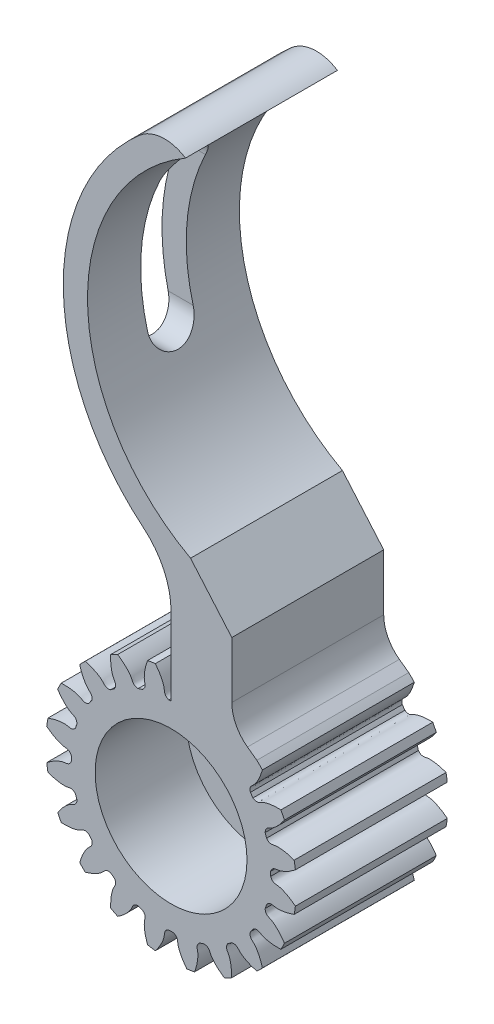
SolidWorks part; units mm, degrees
material "聚脂树脂"
ref_plane "前视基准面" through (0, 0, 0) normal (0, 0, 1) x (1, 0, 0)
ref_plane "上视基准面" through (0, 0, 0) normal (0, 1, 0) x (1, 0, 0)
ref_plane "右视基准面" through (0, 0, 0) normal (1, 0, 0) x (0, 0, -1)
other "Configuration Table"
sketch "草图1" plane through (0, 0, 0) normal (0, 0, 1) x (1, 0, 0)
  circle A0 centre (0, 0) radius 16.5
extrude "凸台-拉伸1" add sketch "草图1" along normal blind 20
ref_axis "基准轴1" through (0, 0, -1.5) along (0, 0, 1)
sketch "草图2" plane through (0, 0, 0) normal (0, 0, 1) x (1, 0, 0)
  line L0 (0, 0) -> (0, 16.5) construction
  circle A0 centre (0, 0) radius 16.5 construction
  arc A1 (0.29, 13.1218) -> (-0.29, 13.1218) centre (0, 0) ccw
  arc A2 (4.7717, 18.7474) -> (-4.7717, 18.7474) centre (0, 0) ccw
  spline S0 degree 3 poles (0.29, 13.1218) (0.9168, 13.3402) (0.8356, 13.7807) (0.9193, 14.205) (0.9283, 14.2463) (0.9395, 14.293) (0.9529, 14.3448) (0.969, 14.4018) (0.9878, 14.4638) (1.0095, 14.5309) (1.0345, 14.6028) (1.0629, 14.6795) (1.0948, 14.7608) (1.1305, 14.8467) (1.1702, 14.9371) (1.2141, 15.0317) (1.2623, 15.1305) (1.315, 15.2334) (1.3725, 15.3401) (1.4349, 15.4506) (1.5023, 15.5646) (1.575, 15.6821) (1.653, 15.8029) (1.7366, 15.9267) (1.826, 16.0534) (1.9211, 16.1829) (2.0223, 16.3149) (2.1296, 16.4493) (2.2432, 16.5859) (2.3632, 16.7244) (2.4897, 16.8646) (2.6229, 17.0065) (2.7628, 17.1496) (2.9095, 17.2939) (3.0632, 17.4391) (3.224, 17.585) (3.3918, 17.7313) (3.567, 17.8779) (3.7493, 18.0245) (3.9391, 18.1709) (4.1363, 18.3167) (4.4122, 18.5125) (4.6259, 18.6545) (4.7717, 18.7474) knots 0 0 0 0 0.165916 0.170906 0.176664 0.183189 0.190482 0.198542 0.207371 0.216967 0.22733 0.238462 0.250361 0.263027 0.276462 0.290664 0.305634 0.321371 0.337876 0.355149 0.37319 0.391998 0.411574 0.431917 0.453028 0.474907 0.497554 0.520968 0.54515 0.570099 0.595817 0.622302 0.649554 0.677575 0.706363 0.735918 0.766242 0.797333 0.829191 0.861818 0.895212 0.929373 1 1 1 1
  spline S1 degree 3 poles (-0.29, 13.1218) (-0.9168, 13.3402) (-0.8356, 13.7807) (-0.9193, 14.205) (-0.9283, 14.2463) (-0.9395, 14.293) (-0.9529, 14.3448) (-0.969, 14.4018) (-0.9878, 14.4638) (-1.0095, 14.5309) (-1.0345, 14.6028) (-1.0629, 14.6795) (-1.0948, 14.7608) (-1.1305, 14.8467) (-1.1702, 14.9371) (-1.2141, 15.0317) (-1.2623, 15.1305) (-1.315, 15.2334) (-1.3725, 15.3401) (-1.4349, 15.4506) (-1.5023, 15.5646) (-1.575, 15.6821) (-1.653, 15.8029) (-1.7366, 15.9267) (-1.826, 16.0534) (-1.9211, 16.1829) (-2.0223, 16.3149) (-2.1296, 16.4493) (-2.2432, 16.5859) (-2.3632, 16.7244) (-2.4897, 16.8646) (-2.6229, 17.0065) (-2.7628, 17.1496) (-2.9095, 17.2939) (-3.0632, 17.4391) (-3.224, 17.585) (-3.3918, 17.7313) (-3.567, 17.8779) (-3.7493, 18.0245) (-3.9391, 18.1709) (-4.1363, 18.3167) (-4.4122, 18.5125) (-4.6259, 18.6545) (-4.7717, 18.7474) knots 0 0 0 0 0.165916 0.170906 0.176664 0.183189 0.190482 0.198542 0.207371 0.216967 0.22733 0.238462 0.250361 0.263027 0.276462 0.290664 0.305634 0.321371 0.337876 0.355149 0.37319 0.391998 0.411574 0.431917 0.453028 0.474907 0.497554 0.520968 0.54515 0.570099 0.595817 0.622302 0.649554 0.677575 0.706363 0.735918 0.766242 0.797333 0.829191 0.861818 0.895212 0.929373 1 1 1 1
extrude "切除-拉伸1" cut sketch "草图2" along normal through all
pattern_circular "阵列(圆周)1" count 20 over 360 about axis through (0, 0, -1.5) along (0, 0, 1) of "切除-拉伸1"
sketch "草图3" plane through (0, 0, 0) normal (0, 0, 1) x (1, 0, 0)
  circle A0 centre (0, 0) radius 15 construction
  dimension "Dn" = 30
sketch "草图4" plane through (0, 0, 0) normal (0, 0, -1) x (-1, 0, 0)
  line L0 (0, 0) -> (67.6919, 0) construction
  line L1 (0, 13.125) -> (0, 76.7697) construction
  line L2 (-15, 0) -> (-15, 67.6903) construction
  line L6 (-7.9502, 14.4584) -> (-11.294, 12.029)
  line L7 (-8, 0) -> (-8, 28.5)
  line L8 (0, 28.5) -> (0, 0)
  line L9 (-2.6766, 80) -> (-1.9024, 76)
  line L10 (-8, 0) -> (0, 0)
  circle A2 centre (-15, 53.54) radius 26 construction
  arc A4 (-8, 28.5) -> (-1.9024, 76) centre (-15, 53.54) ccw
  arc A6 (0.29, 13.1218) -> (-0.29, 13.1218) centre (0, 0) ccw construction
  arc A7 (-2.0665, 16.3701) -> (-3.0932, 16.2075) centre (0, 0) ccw construction
  arc A8 (-3.7791, 12.5692) -> (-4.3306, 12.39) centre (0, 0) ccw construction
  arc A9 (-7.024, 14.9303) -> (-7.9502, 14.4584) centre (0, 0) ccw construction
  arc A10 (0, 13.125) -> (-0.29, 13.1218) centre (0, 0) ccw
  arc A11 (-2.0665, 16.3701) -> (-3.0932, 16.2075) centre (0, 0) ccw
  arc A12 (-3.7791, 12.5692) -> (-4.3306, 12.39) centre (0, 0) ccw
  arc A13 (-7.024, 14.9303) -> (-7.9502, 14.4584) centre (0, 0) ccw
  arc A14 (-7.4782, 10.7862) -> (-7.9474, 10.4453) centre (0, 0) ccw construction
  arc A15 (-7.4782, 10.7862) -> (-7.9474, 10.4453) centre (0, 0) ccw
  circle A16 centre (0, 0) radius 12.5
  circle A17 centre (-15, 53.54) radius 29.189 construction
  arc A18 (0, 28.5) -> (-2.6766, 80) centre (-15, 53.54) ccw
  spline S2 degree 3 poles (2893.0227, 805.0918) (-33.8284, -4.4422) (0.2784, 8.134) (-0.9224, 14.2207) (-0.9359, 14.2793) (-0.9529, 14.3448) (-0.969, 14.4018) (-0.9951, 14.4881) (-1.0357, 14.6084) (-1.0961, 14.7664) (-1.1716, 14.9426) (-1.2638, 15.1361) (-1.3741, 15.3456) (-1.5041, 15.5702) (-1.6549, 15.8084) (-1.7965, 16.0133) (-1.9211, 16.1829) (-20.8455, 40.8769) (-174.4366, -39.8531) (2991.2279, 211.9962) knots -2.350827 -2.350827 -2.350827 -2.350827 0.165916 0.170906 0.183189 0.190482 0.198542 0.207371 0.22733 0.250361 0.276462 0.305634 0.337876 0.37319 0.411574 0.453028 0.474907 0.497554 13.160601 13.160601 13.160601 13.160601 only from (-0.29, 13.1218) to (-2.0665, 16.3701) construction
  spline S3 degree 3 poles (-3000.2151, -128.3054) (33.5455, 6.2288) (-2.7783, 7.6499) (-3.5171, 13.8097) (-3.5224, 13.8696) (-3.5265, 13.9372) (-3.5289, 13.9963) (-3.5307, 14.0865) (-3.5293, 14.2134) (-3.5206, 14.3824) (-3.5033, 14.5733) (-3.4754, 14.7858) (-3.4352, 15.0192) (-3.381, 15.2729) (-3.3111, 15.5461) (-3.2398, 15.7847) (-3.1737, 15.9845) (7.1936, 45.3178) (178.2143, 16.0013) (-2910.3372, -722.7198) knots -1.858258 -1.858258 -1.858258 -1.858258 0.658484 0.663474 0.675757 0.68305 0.691111 0.699939 0.719899 0.742929 0.76903 0.798202 0.830445 0.865758 0.904142 0.945597 0.967475 0.990122 13.653169 13.653169 13.653169 13.653169 only from (-3.7791, 12.5692) to (-3.0932, 16.2075) construction
  spline S4 degree 3 poles (2502.641, 1659.681) (-30.8, -14.6784) (-2.2488, 7.8219) (-5.2717, 13.2396) (-5.3027, 13.2912) (-5.3391, 13.3482) (-5.3719, 13.3975) (-5.4235, 13.4715) (-5.4992, 13.5733) (-5.6055, 13.705) (-5.7318, 13.8492) (-5.8792, 14.0047) (-6.0489, 14.1699) (-6.2419, 14.3433) (-6.459, 14.5233) (-6.6569, 14.6744) (-6.8279, 14.7972) (-32.4569, 32.4346) (-153.5838, -91.8064) (2779.3163, 1125.9607) knots -2.350827 -2.350827 -2.350827 -2.350827 0.165916 0.170906 0.183189 0.190482 0.198542 0.207371 0.22733 0.250361 0.276462 0.305634 0.337876 0.37319 0.411574 0.453028 0.474907 0.497554 13.160601 13.160601 13.160601 13.160601 only from (-4.3306, 12.39) to (-7.024, 14.9303) construction
  spline S5 degree 3 poles (-0.29, 13.1218) (-0.9168, 13.3402) (-0.8356, 13.7807) (-0.9224, 14.2207) (-0.9359, 14.2793) (-0.9529, 14.3448) (-0.969, 14.4018) (-0.9951, 14.4881) (-1.0357, 14.6084) (-1.0961, 14.7664) (-1.1716, 14.9426) (-1.2638, 15.1361) (-1.3741, 15.3456) (-1.5041, 15.5702) (-1.6549, 15.8084) (-1.828, 16.0589) (-1.969, 16.2466) (-2.0515, 16.3512) (-2.0665, 16.3701) knots 0 0 0 0 0.165916 0.170906 0.183189 0.190482 0.198542 0.207371 0.22733 0.250361 0.276462 0.305634 0.337876 0.37319 0.411574 0.453028 0.497554 0.507432 0.507432 0.507432 0.507432
  spline S6 degree 3 poles (-3.7791, 12.5692) (-3.2504, 12.9706) (-3.4637, 13.3644) (-3.5171, 13.8097) (-3.5224, 13.8696) (-3.5265, 13.9372) (-3.5289, 13.9963) (-3.5307, 14.0865) (-3.5293, 14.2134) (-3.5206, 14.3824) (-3.5033, 14.5733) (-3.4754, 14.7858) (-3.4352, 15.0192) (-3.381, 15.2729) (-3.3111, 15.5461) (-3.224, 15.8378) (-3.1479, 16.0599) (-3.1017, 16.1848) (-3.0932, 16.2075) knots 0.492568 0.492568 0.492568 0.492568 0.658484 0.663474 0.675757 0.68305 0.691111 0.699939 0.719899 0.742929 0.76903 0.798202 0.830445 0.865758 0.904142 0.945597 0.990122 1 1 1 1
  spline S7 degree 3 poles (-4.3306, 12.39) (-4.9943, 12.404) (-5.0532, 12.848) (-5.2717, 13.2396) (-5.3027, 13.2912) (-5.3391, 13.3482) (-5.3719, 13.3975) (-5.4235, 13.4715) (-5.4992, 13.5733) (-5.6055, 13.705) (-5.7318, 13.8492) (-5.8792, 14.0047) (-6.0489, 14.1699) (-6.2419, 14.3433) (-6.459, 14.5233) (-6.701, 14.7081) (-6.8931, 14.843) (-7.0039, 14.9169) (-7.024, 14.9303) knots 0 0 0 0 0.165916 0.170906 0.183189 0.190482 0.198542 0.207371 0.22733 0.250361 0.276462 0.305634 0.337876 0.37319 0.411574 0.453028 0.497554 0.507432 0.507432 0.507432 0.507432
  spline S8 degree 3 poles (-2813.7256, -1049.1431) (29.9789, 16.29) (-5.0063, 6.4169) (-7.6124, 12.047) (-7.636, 12.1023) (-7.6607, 12.1653) (-7.6812, 12.2208) (-7.7108, 12.3061) (-7.7487, 12.4272) (-7.7927, 12.5905) (-7.8352, 12.7775) (-7.8743, 12.9882) (-7.9082, 13.2226) (-7.9351, 13.4806) (-7.9531, 13.762) (-7.959, 14.011) (-7.9578, 14.2215) (-7.1625, 45.3227) (164.5472, 70.2894) (-2544.5625, -1586.6911) knots -1.858258 -1.858258 -1.858258 -1.858258 0.658484 0.663474 0.675757 0.68305 0.691111 0.699939 0.719899 0.742929 0.76903 0.798202 0.830445 0.865758 0.904142 0.945597 0.967475 0.990122 13.653169 13.653169 13.653169 13.653169 only from (-7.4782, 10.7862) to (-7.9502, 14.4584) construction
  spline S9 degree 3 poles (1867.2834, 2351.809) (-24.7567, -23.4777) (-4.5558, 6.7442) (-9.105, 10.9626) (-9.1503, 11.0021) (-9.2026, 11.0451) (-9.2491, 11.0817) (-9.321, 11.1362) (-9.4245, 11.2097) (-9.5662, 11.302) (-9.7309, 11.4002) (-9.9192, 11.5025) (-10.1316, 11.6072) (-10.3687, 11.7125) (-10.6308, 11.8165) (-10.8658, 11.8991) (-11.0663, 11.963) (-40.8912, 20.8174) (-117.6971, -134.7731) (2295.3459, 1929.7082) knots -2.350827 -2.350827 -2.350827 -2.350827 0.165916 0.170906 0.183189 0.190482 0.198542 0.207371 0.22733 0.250361 0.276462 0.305634 0.337876 0.37319 0.411574 0.453028 0.474907 0.497554 13.160601 13.160601 13.160601 13.160601 only from (-7.9474, 10.4453) to (-11.294, 12.029) construction
  spline S10 degree 3 poles (-7.4782, 10.7862) (-7.0995, 11.3313) (-7.424, 11.64) (-7.6124, 12.047) (-7.636, 12.1023) (-7.6607, 12.1653) (-7.6812, 12.2208) (-7.7108, 12.3061) (-7.7487, 12.4272) (-7.7927, 12.5905) (-7.8352, 12.7775) (-7.8743, 12.9882) (-7.9082, 13.2226) (-7.9351, 13.4806) (-7.9531, 13.762) (-7.9603, 14.0664) (-7.9566, 14.3011) (-7.9513, 14.4342) (-7.9502, 14.4584) knots 0.492568 0.492568 0.492568 0.492568 0.658484 0.663474 0.675757 0.68305 0.691111 0.699939 0.719899 0.742929 0.76903 0.798202 0.830445 0.865758 0.904142 0.945597 0.990122 1 1 1 1
  spline S11 degree 3 poles (-7.9474, 10.4453) (-8.5829, 10.2536) (-8.7761, 10.6576) (-9.105, 10.9626) (-9.1503, 11.0021) (-9.2026, 11.0451) (-9.2491, 11.0817) (-9.321, 11.1362) (-9.4245, 11.2097) (-9.5662, 11.302) (-9.7309, 11.4002) (-9.9192, 11.5025) (-10.1316, 11.6072) (-10.3687, 11.7125) (-10.6308, 11.8165) (-10.9181, 11.9175) (-11.1425, 11.9864) (-11.2707, 12.0225) (-11.294, 12.029) knots 0 0 0 0 0.165916 0.170906 0.183189 0.190482 0.198542 0.207371 0.22733 0.250361 0.276462 0.305634 0.337876 0.37319 0.411574 0.453028 0.497554 0.507432 0.507432 0.507432 0.507432
  dimension "D4" = 52
  dimension "D5" = 80
  dimension "D3" = 25
  dimension "D1" = 15
  dimension "D2" = 28.5
  dimension "D6" = 76
  dimension "D8" = 8
  dimension "D9" = 28.5
extrude "凸台-拉伸2" add sketch "草图4" against normal blind 20 contours S7 A12 S6 A11 S5 A10 L8 A18 L9 A4 L7 L6 A13 | S11 L7 L6 | L6 S11 A15 S10 region at (7.2884, 21.4611, 0) region at (9.051, 12.2758, 0)
fillet "圆角1" radius 10 1 edges at (0, 28.5, 10)
fillet "圆角2" radius 5 2 edges at (8, 14.4222, 10) (2.6766, 80, 10)
sketch "草图5" plane through (0, 0, 0) normal (0, 0, -1) x (-1, 0, 0)
  line L0 (0, 0) -> (47.9973, 0) construction
  line L1 (0, 0) -> (0, 54.3289) construction
sketch "草图7" plane through (0, 0, 20) normal (0, 0, 1) x (1, 0, 0)
  line L0 (0, 0) -> (42.9933, 0) construction
  line L1 (0, 0) -> (0, 51.6895) construction
  circle A0 centre (0, 0) radius 10
  dimension "D1" = 20
extrude "切除-拉伸2" cut sketch "草图7" against normal blind 12
sketch "草图8" plane through (0, 0, 8) normal (0, 0, 1) x (1, 0, 0)
  line L0 (0, 0) -> (25.4464, 0) construction
  line L1 (0, 0) -> (0, 31.9913) construction
  circle A0 centre (0, 0) radius 3.5
  circle A1 centre (0, 7) radius 1.5
  circle A2 centre (7, 0) radius 1.5
  circle A3 centre (0, -7) radius 1.5
  circle A4 centre (-7, 0) radius 1.5
  dimension "D1" = 3
  dimension "D2" = 7
  dimension "D4" = 3
  dimension "D3" = 7
  dimension "D5" = 7
extrude "切除-拉伸3" cut sketch "草图8" against normal blind 10
chamfer "倒角1" distance 5 angle 45 1 edges at (8, 28.5, 10) first distance on face at (8, 22.7349, 10)
sketch "草图10" plane through (0, 0, 0) normal (0, 0, -1) x (-1, 0, 0)
  circle A0 centre (0, 0) radius 10
  circle A1 centre (-7, 0) radius 1.5 construction
  circle A2 centre (0, -7) radius 1.5 construction
  circle A3 centre (0, 0) radius 3.5 construction
  circle A4 centre (7, 0) radius 1.5 construction
  circle A5 centre (0, 7) radius 1.5 construction
  circle A6 centre (-7, 0) radius 1.5
  circle A7 centre (0, -7) radius 1.5
  circle A8 centre (0, 0) radius 3.5
  circle A9 centre (7, 0) radius 1.5
  circle A10 centre (0, 7) radius 1.5
  dimension "D1" = 20
extrude "凸台-拉伸3" add sketch "草图10" along normal blind 2
fillet "圆角3" radius 2 1 edges at (10, 0, 0)
sketch "草图11" plane through (0, 0, 0) normal (1, 0, 0) x (0, 0, -1)
  line L0 (-10, 46.72) -> (-10, 64.72) construction
  line L1 (-13, 46.72) -> (-13, 64.72)
  line L2 (-7, 46.72) -> (-7, 64.72)
  line L3 (0, 30.7059) -> (0, 76) construction
  arc A0 (-13, 46.72) -> (-7, 46.72) centre (-10, 46.72) ccw
  arc A1 (-7, 64.72) -> (-13, 64.72) centre (-10, 64.72) ccw
  point P2 (-10, 55.72)
  dimension "D2" = 3
  dimension "D1" = 18
  dimension "D3" = 10
  dimension "D4" = 55.72
extrude "切除-拉伸4" cut sketch "草图11" against normal blind 24
